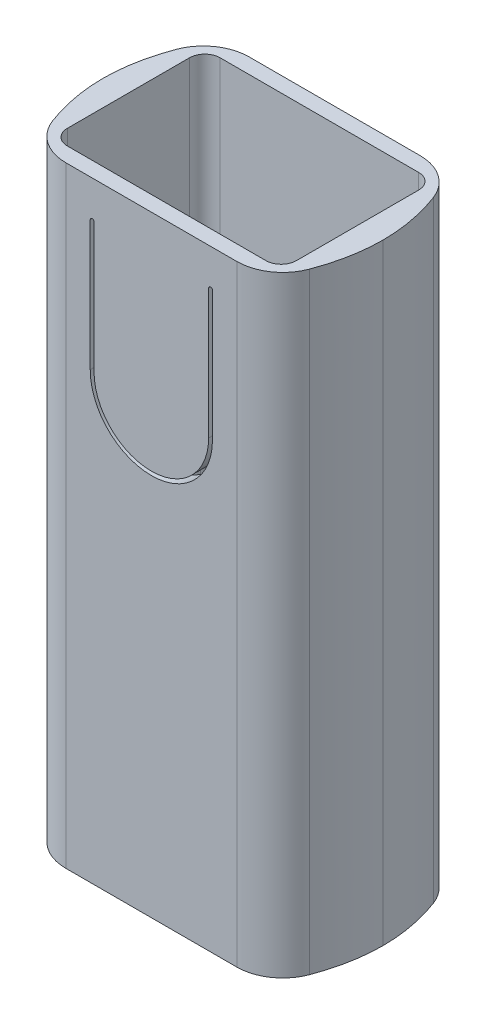
SolidWorks part; units mm, degrees
ref_plane "Front Plane" through (0, 0, 0) normal (0, 0, 1) x (1, 0, 0)
ref_plane "Top Plane" through (0, 0, 0) normal (0, 1, 0) x (1, 0, 0)
ref_plane "Right Plane" through (0, 0, 0) normal (1, 0, 0) x (0, 0, -1)
ref_plane "Plane1" through (0, 58, 0) normal (0, 1, 0) x (1, 0, 0)
sketch "Sketch8" plane through (0, 58, 0) normal (0, 1, 0) x (1, 0, 0)
  line L1 (-15, -8) -> (-15, 8)
  line L2 (-13, 10) -> (13, 10)
  line L5 (-15, 10) -> (-14.2911, 9.5274) construction
  line L8 (-11.1948, 12) -> (11.1948, 12)
  line L11 (-15.4079, 10.272) -> (-14.2911, 9.5274) construction
  line L12 (15.4079, 10.272) -> (14.2911, 9.5274) construction
  line L15 (0, 12) -> (0, -12) construction
  line L16 (15, 10) -> (14.2911, 9.5274) construction
  line L17 (15, -8) -> (15, 8)
  line L18 (15, -10) -> (14.2911, -9.5274) construction
  line L19 (15.4079, -10.272) -> (14.2911, -9.5274) construction
  line L20 (-18.3347, 0) -> (18.3347, 0) construction
  line L21 (0, 0) -> (0, 12) construction
  line L22 (-15.4079, -10.272) -> (-14.2911, -9.5274) construction
  line L23 (-15, -10) -> (-14.2911, -9.5274) construction
  line L24 (-11.1948, -12) -> (11.1948, -12)
  line L25 (-13, -10) -> (13, -10)
  arc A8 (-13, 10) -> (-15, 8) centre (-13, 8) ccw
  arc A10 (-11.1948, 12) -> (-16.8117, 8.1097) centre (-11.1948, 6) ccw
  arc A11 (11.1948, 12) -> (16.8117, 8.1097) centre (11.1948, 6) cw
  arc A12 (13, 10) -> (15, 8) centre (13, 8) cw
  arc A13 (13, -10) -> (15, -8) centre (13, -8) ccw
  arc A14 (11.1948, -12) -> (16.8117, -8.1097) centre (11.1948, -6) ccw
  arc A15 (-11.1948, -12) -> (-16.8117, -8.1097) centre (-11.1948, -6) cw
  arc A16 (-13, -10) -> (-15, -8) centre (-13, -8) cw
  spline S0 degree 3 poles (-18.3347, 0) (-18.3272, 2.7261) (-17.8195, 5.4265) (-16.8117, 8.1097) knots 0.502499 0.502499 0.502499 0.502499 0.837905 0.837905 0.837905 0.837905
  spline S1 degree 3 poles (18.3347, 0) (18.3272, 2.7261) (17.8195, 5.4265) (16.8117, 8.1097) knots 0.502499 0.502499 0.502499 0.502499 0.837905 0.837905 0.837905 0.837905
  spline S2 degree 3 poles (18.3347, 0) (18.3272, -2.7261) (17.8195, -5.4265) (16.8117, -8.1097) knots 0.502499 0.502499 0.502499 0.502499 0.837905 0.837905 0.837905 0.837905
  spline S3 degree 3 poles (-18.3347, 0) (-18.3272, -2.7261) (-17.8195, -5.4265) (-16.8117, -8.1097) knots 0.502499 0.502499 0.502499 0.502499 0.837905 0.837905 0.837905 0.837905
  point P0 (0, 0)
  point P8 (-15, 0)
  point P19 (-15, 10)
  point P26 (0, 0)
  point P27 (-12, 9.5)
  point P36 (0, 10)
  point P37 (12, 9.5)
  point P51 (-18.3347, 0)
  point P53 (-15, 0)
  point P55 (12, -9.5)
  point P61 (15, 0)
  point P62 (0, -10)
  point P63 (-12, -9.5)
  dimension "D3" = 8.2959
  dimension "D6" = 3.8903
  dimension "D2" = 6
  dimension "D7" = 2
  dimension "D1" = 13.9635
  dimension "D4" = 3.3347
  dimension "D5" = 1.523
  dimension "D8" = 2
  dimension "D9" = 15
sketch "Sketch11" plane through (0, 58, 0) normal (0, 1, 0) x (1, 0, 0)
  line L10 (-13, 10) -> (13, 10) construction
  line L11 (13, 10) -> (15, 10)
  line L13 (-13, 7.4379) -> (-13, 10)
  line L19 (15, 10) -> (15, 6.9379)
  line L20 (15, 6.9379) -> (13.5, 6.9379)
  line L21 (13, 7.4379) -> (13, 10)
  line L22 (-15, 6.9379) -> (-13.5, 6.9379)
  line L23 (-15, 10) -> (-15, 6.9379)
  line L24 (-13, 10) -> (-15, 10)
  arc A4 (13.5, 6.9379) -> (13, 7.4379) centre (13.5, 7.4379) cw
  arc A5 (-13.5, 6.9379) -> (-13, 7.4379) centre (-13.5, 7.4379) ccw
  dimension "D1" = 0.5
extrude "Boss-Extrude4" add sketch "Sketch8" along normal blind 80
extrude "Boss-Extrude5" add sketch "Sketch11" along normal blind 57
sketch "Sketch12" plane through (0, 0, 12) normal (0, 0, 1) x (1, 0, 0)
  line L1 (0, 116.1342) -> (0, 135.2209) construction
  line L2 (7.5, 133.1342) -> (7.5, 116.1342)
  line L3 (-7.5, 133.1342) -> (-7.5, 116.1342)
  line L4 (8, 133.1342) -> (8, 116.1342)
  line L5 (-8, 116.1342) -> (-8, 133.1342)
  line L6 (7.5, 130.5553) -> (0, 130.5553) construction
  line L7 (0, 130.5553) -> (-7.5, 130.5553) construction
  line L8 (-11.1948, 138) -> (11.1948, 138) construction
  line L9 (0, 138) -> (0, 58) construction
  line L10 (13.2, 58) -> (-13.2, 58) construction
  arc A1 (8, 116.1342) -> (-8, 116.1342) centre (0, 116.1342) cw
  arc A2 (7.5, 133.1342) -> (8, 133.1342) centre (7.75, 133.1342) cw
  arc A3 (-8, 133.1342) -> (-7.5, 133.1342) centre (-7.75, 133.1342) cw
  arc A4 (7.5, 116.1342) -> (-7.5, 116.1342) centre (0, 116.1342) cw
  point P1 (0, 108.6342)
  point P14 (0, 108.1342)
  point P20 (0.4953, 108.6342)
  point P23 (0, 138)
  dimension "D5" = 0.5
  dimension "D1" = 15
  dimension "D2" = 0.5
  dimension "D3" = 0.5
  dimension "D4" = 25
  dimension "D7" = 4.6657
extrude "Cut-Extrude1" cut sketch "Sketch12" against normal blind 2
sketch "Sketch14" plane through (0, 115, 0) normal (0, 1, 0) x (1, 0, 0)
  line L3 (13, 10) -> (13, 7.4379)
  line L4 (13.5, 6.9379) -> (15, 6.9379)
  line L5 (15, 6.9379) -> (15, 8)
  line L6 (13, 10) -> (13, 7.4379)
  line L7 (13.5, 6.9379) -> (15, 6.9379)
  line L8 (15, 6.9379) -> (15, 8)
  arc A2 (15, 8) -> (13, 10) centre (13, 8) ccw
  arc A3 (13, 7.4379) -> (13.5, 6.9379) centre (13.5, 7.4379) ccw
  arc A4 (15, 8) -> (13, 10) centre (13, 8) ccw
  arc A5 (13, 7.4379) -> (13.5, 6.9379) centre (13.5, 7.4379) ccw
  dimension "D1" = 0
ref_plane "Plane2" through (0, 128, 0) normal (0, 1, 0) x (1, 0, 0)
sketch "Sketch15" plane through (0, 128, 0) normal (0, 1, 0) x (1, 0, 0)
  line L0 (13, 10) -> (15, 8)
  arc A0 (15, 8) -> (13, 10) centre (13, 8) ccw construction
  arc A1 (15, 8) -> (13, 10) centre (13, 8) ccw
  point P2 (13, 10)
  point P5 (15, 8)
  point P7 (15, 10)
chamfer "Chamfer1" distance 0.5 angle 80 6 edges at (-14.25, 115, -6.9379) (-13, 115, -8.719) (-13.1464, 115, -7.0844) (13, 115, -8.719) (14.25, 115, -6.9379) (13.1464, 115, -7.0844)
